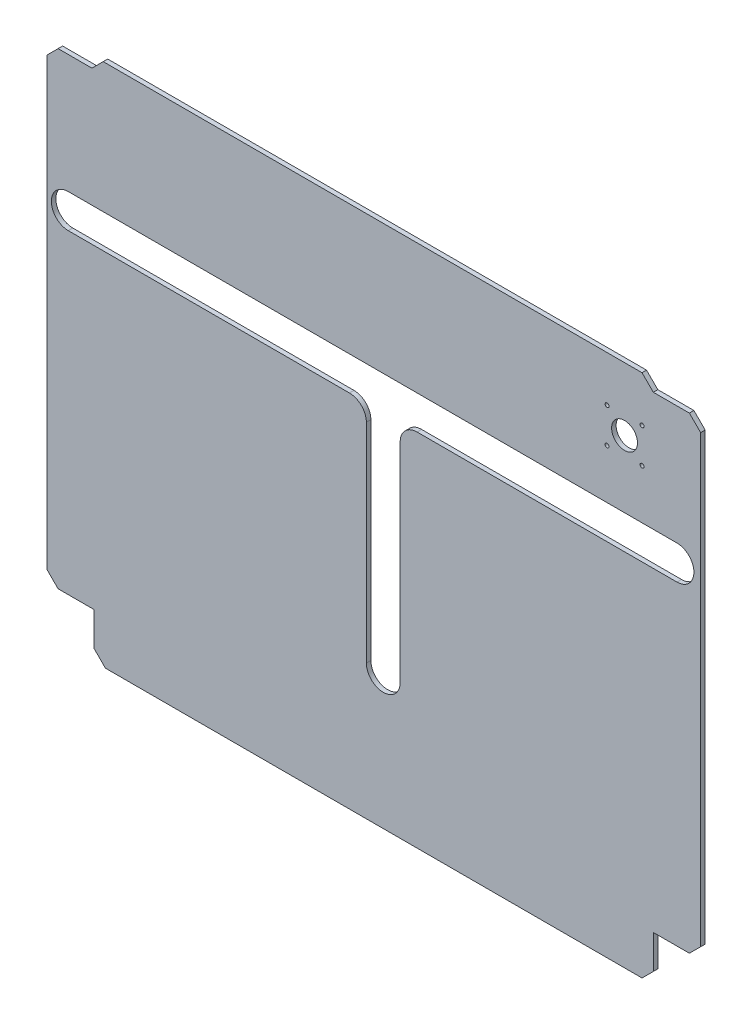
SolidWorks part; units mm, degrees
ref_plane "Front Plane" through (0, 0, 0) normal (0, 0, 1) x (1, 0, 0)
ref_plane "Top Plane" through (0, 0, 0) normal (0, 1, 0) x (1, 0, 0)
ref_plane "Right Plane" through (0, 0, 0) normal (1, 0, 0) x (0, 0, -1)
sketch "Sketch1" plane through (0, 0, 0) normal (0, 0, 1) x (1, 0, 0)
  line L0 (-39.6803, -5.0048) -> (0.3197, -5.0048)
  line L1 (0.3197, 4.9952) -> (0.3197, -5.0048)
  line L2 (498.3197, 4.9952) -> (498.3197, -5.0048)
  line L3 (2.3197, -460.0048) -> (2.3197, -420.0048)
  line L4 (498.3197, -5.0048) -> (540.3197, -5.0048)
  line L5 (498.3197, -5.0048) -> (498.3197, -420.0048) construction
  line L6 (540.3197, -5.0048) -> (540.3197, -420.0048)
  line L7 (0.3197, 4.9952) -> (498.3197, 4.9952)
  line L8 (2.3197, -460.0048) -> (498.3197, -460.0048)
  line L9 (2.3197, -420.0048) -> (-39.6803, -420.0048)
  line L10 (540.3197, -420.0048) -> (498.3197, -420.0048)
  line L11 (488.3197, -23.973) -> (488.3197, -80.4204) construction
  line L12 (-39.6803, -420.0048) -> (-39.6803, -5.0048)
  line L13 (488.3197, -35.4482) -> (457.3197, -35.4482) construction
  line L14 (498.3197, -420.0048) -> (498.3197, -460.0048)
  line L15 (457.3197, -35.4482) -> (457.3197, -66.4482) construction
  line L16 (457.3197, -66.4482) -> (488.3197, -66.4482) construction
  line L17 (488.3197, -66.4482) -> (457.3197, -35.4482) construction
  circle A0 centre (457.3197, -35.4482) radius 1.75
  circle A1 centre (457.3197, -66.4482) radius 1.75
  circle A2 centre (488.3197, -66.4482) radius 1.75
  circle A3 centre (488.3197, -35.4482) radius 1.75
  circle A4 centre (472.8197, -50.9482) radius 11.5
  dimension "D6" = 23
  dimension "D7" = 3.5
  dimension "D1" = 415
  dimension "D2" = 10
  dimension "D3" = 580
  dimension "D4" = 40
  dimension "D5" = 31
  dimension "D8" = 10
extrude "Boss-Extrude1" add sketch "Sketch1" along normal blind 4
chamfer "Chamfer1" distance 10 angle 45 2 edges at (498.3197, 4.9952, 2) (0.3197, 4.9952, 2)
chamfer "Chamfer2" distance 10 angle 45 6 edges at (540.3197, -5.0048, 2) (-39.6803, -5.0048, 2) (-39.6803, -420.0048, 2) (2.3197, -460.0048, 2) (498.3197, -460.0048, 2) (540.3197, -420.0048, 2)
sketch "Sketch2" plane through (0, 0, 4) normal (0, 0, 1) x (1, 0, 0)
  line L0 (-20.6803, -110.3334) -> (519.3197, -110.3334)
  line L1 (519.3197, -140.3334) -> (-20.6803, -140.3334)
  line L2 (12.3197, -460.0048) -> (488.3197, -460.0048) construction
  line L4 (488.3197, 4.9952) -> (10.3197, 4.9952) construction
  arc A0 (-20.6803, -110.3334) -> (-20.6803, -140.3334) centre (-20.6803, -125.3334) ccw
  arc A1 (519.3197, -140.3334) -> (519.3197, -110.3334) centre (519.3197, -125.3334) ccw
  point P8 (249.3197, -140.3334)
  point P11 (249.3197, 4.9952)
  point P12 (534.3197, -125.3334)
  dimension "D2" = 15
  dimension "D1" = 540
  dimension "D3" = 0
extrude "Cut-Extrude1" cut sketch "Sketch2" against normal blind 10
sketch "Sketch3" plane through (0, 0, 0) normal (0, 0, -1) x (-1, 0, 0)
  line L0 (-273.7635, -140.3334) -> (-273.7635, -340.3334)
  line L1 (20.6803, -140.3334) -> (-519.3197, -140.3334) construction
  line L2 (-243.7635, -340.3334) -> (-243.7635, -140.3334)
  line L3 (-243.7635, -140.3334) -> (-273.7635, -140.3334)
  arc A0 (-273.7635, -340.3334) -> (-243.7635, -340.3334) centre (-258.7635, -340.3334) ccw
  dimension "D2" = 15
  dimension "D1" = 200
extrude "Cut-Extrude2" cut sketch "Sketch3" against normal blind 10
fillet "Fillet1" radius 15 2 edges at (243.7635, -140.3334, 2) (273.7635, -140.3334, 2)
